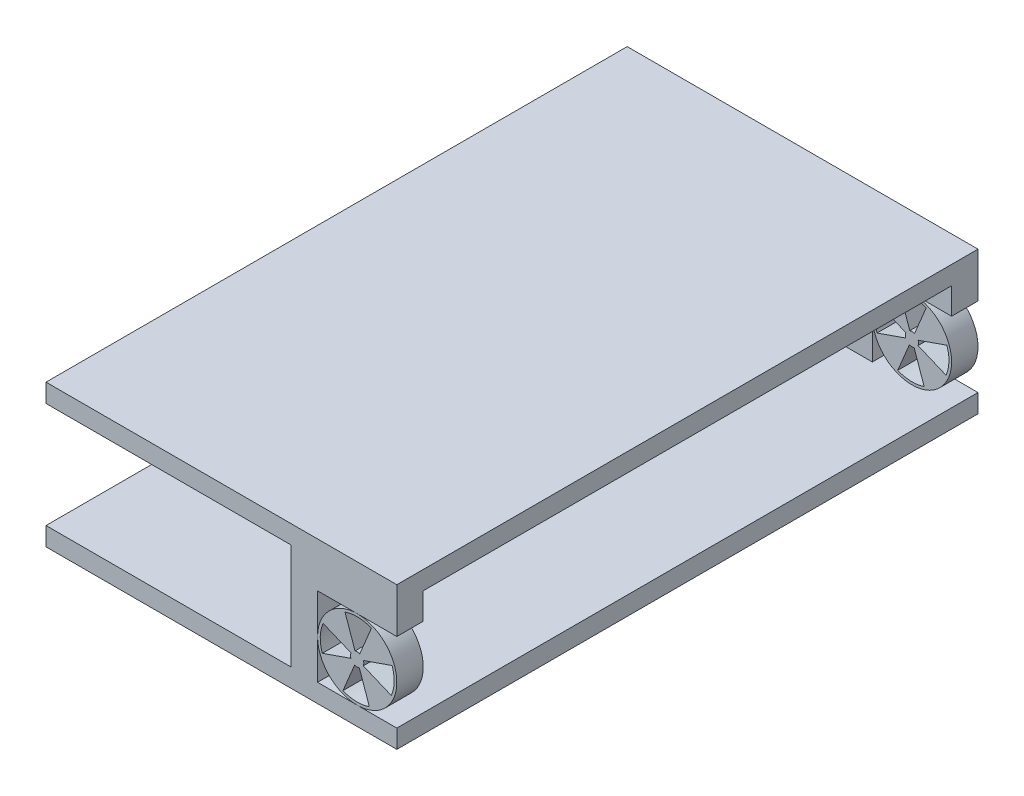
SolidWorks part; units mm, degrees
ref_plane "Front Plane" through (0, 0, 0) normal (0, 0, 1) x (1, 0, 0)
ref_plane "Top Plane" through (0, 0, 0) normal (0, 1, 0) x (1, 0, 0)
ref_plane "Right Plane" through (0, 0, 0) normal (1, 0, 0) x (0, 0, -1)
sketch "Sketch2" plane through (0, 0, 0) normal (0, 1, 0) x (1, 0, 0)
  line L1 (-173.99, 279.4) -> (173.99, 279.4)
  line L2 (-173.99, 279.4) -> (-173.99, -279.4)
  line L3 (-173.99, -279.4) -> (173.99, -279.4)
  line L4 (173.99, 279.4) -> (173.99, -279.4)
  line L5 (-173.99, 279.4) -> (173.99, -279.4) construction
  line L6 (-173.99, -279.4) -> (173.99, 279.4) construction
  point P0 (0, 0)
  dimension "D1" = 558.8
  dimension "D2" = 347.98
extrude "Boss-Extrude1" add sketch "Sketch2" along normal blind 17.78
sketch "Sketch3" plane through (0, 17.78, 0) normal (0, 1, 0) x (1, 0, 0)
  line L0 (72.39, -279.4) -> (72.39, -254)
  line L1 (-173.99, -279.4) -> (173.99, -279.4) construction
  line L2 (72.39, -254) -> (97.79, -254)
  line L3 (97.79, -254) -> (97.79, -279.4)
  line L4 (97.79, -279.4) -> (72.39, -279.4)
  line L5 (173.99, -279.4) -> (173.99, 279.4) construction
  line L6 (0, 0) -> (152.5778, 0) construction
  line L7 (97.79, 254) -> (97.79, 279.4)
  line L8 (97.79, 279.4) -> (72.39, 279.4)
  line L9 (72.39, 279.4) -> (72.39, 254)
  line L10 (72.39, 254) -> (97.79, 254)
  dimension "D1" = 101.6
  dimension "D2" = 76.2
  dimension "D3" = 25.4
extrude "Boss-Extrude2" add sketch "Sketch3" along normal blind 101.6
sketch "Sketch4" plane through (97.79, 0, 0) normal (1, 0, 0) x (0, 0, -1)
  line L0 (-279.4, 119.38) -> (-279.4, 93.98)
  line L1 (-279.4, 119.38) -> (-279.4, 17.78) construction
  line L2 (-279.4, 93.98) -> (-254, 93.98)
  line L3 (-254, 119.38) -> (-254, 17.78) construction
  line L4 (-254, 93.98) -> (-254, 119.38)
  line L5 (-254, 119.38) -> (-279.4, 119.38)
  line L6 (254, 119.38) -> (254, 93.98)
  line L7 (254, 119.38) -> (254, 17.78) construction
  line L8 (254, 93.98) -> (279.4, 93.98)
  line L9 (279.4, 119.38) -> (279.4, 17.78) construction
  line L10 (279.4, 93.98) -> (279.4, 119.38)
  line L11 (279.4, 119.38) -> (254, 119.38)
  dimension "D1" = 25.4
  dimension "D2" = 25.4
extrude "Boss-Extrude3" add sketch "Sketch4" along normal up to vertex (76.2 mm away) up to point (173.99, 17.78, 279.4)
sketch "Sketch5" plane through (0, 0, 0) normal (0, 0, 1) x (1, 0, 0)
  line L0 (135.89, 93.98) -> (135.89, 17.78) construction
  line L1 (173.99, 93.98) -> (97.79, 93.98) construction
  line L2 (97.79, 17.78) -> (173.99, 17.78) construction
  line L3 (97.79, 55.88) -> (178.4367, 55.88) construction
  line L4 (97.79, 93.98) -> (97.79, 17.78) construction
  circle A0 centre (135.89, 55.88) radius 38.1
  dimension "D1" = 76.2
extrude "Boss-Extrude4" add sketch "Sketch5" against normal blind 25.4 from surface separate body starting at face at (68.834, 49.784, 279.4)
extrude "Boss-Extrude5" add sketch "Sketch5<2>" along normal blind 25.4 from surface separate body starting at face at (68.834, 49.784, -279.4)
sketch "Sketch5<2>" plane through (0, 0, 0) normal (0, 0, 1) x (1, 0, 0) same geometry as "Sketch5"
sketch "Sketch6" plane through (0, 0, 279.4) normal (0, 0, 1) x (1, 0, 0)
  line L0 (135.89, 93.98) -> (135.89, 17.78) construction
  line L1 (173.99, 93.98) -> (97.79, 93.98) construction
  line L2 (97.79, 17.78) -> (173.99, 17.78) construction
  line L3 (97.79, 55.88) -> (173.99, 55.88) construction
  line L4 (97.79, 93.98) -> (97.79, 17.78) construction
  line L5 (124.1846, 89.4582) -> (133.7998, 61.8761)
  line L6 (149.5734, 88.7019) -> (138.3335, 61.7411)
  line L7 (169.4682, 67.5854) -> (141.8861, 57.9702)
  line L8 (168.7119, 42.1966) -> (141.7511, 53.4365)
  line L9 (147.5954, 22.3018) -> (137.9802, 49.8839)
  line L10 (122.2066, 23.0581) -> (133.4465, 50.0189)
  line L11 (102.3118, 44.1746) -> (129.8939, 53.7898)
  line L12 (103.0681, 69.5634) -> (130.0289, 58.3235)
  circle A0 centre (135.89, 55.88) radius 38.1 construction
  arc A1 (124.1846, 89.4582) -> (149.5734, 88.7019) centre (135.89, 55.88) cw
  arc A3 (169.4682, 67.5854) -> (168.7119, 42.1966) centre (135.89, 55.88) cw
  arc A5 (147.5954, 22.3018) -> (122.2066, 23.0581) centre (135.89, 55.88) cw
  arc A7 (102.3118, 44.1746) -> (103.0681, 69.5634) centre (135.89, 55.88) cw
  arc A8 (138.3335, 61.7411) -> (133.7998, 61.8761) centre (135.89, 55.88) ccw
  arc A9 (130.0289, 58.3235) -> (129.8939, 53.7898) centre (135.89, 55.88) ccw
  arc A10 (133.4465, 50.0189) -> (137.9802, 49.8839) centre (135.89, 55.88) ccw
  arc A11 (141.7511, 53.4365) -> (141.8861, 57.9702) centre (135.89, 55.88) ccw
  point P37 (135.89, 55.88)
  dimension "D2" = 4
extrude "Cut-Extrude2" cut sketch "Sketch6" against normal blind 1270
extrude "Boss-Extrude6" add sketch "Sketch2<2>" along normal blind 17.78 from surface starting at face at (123.19, 119.38, 266.7)
sketch "Sketch2<2>" plane through (0, 0, 0) normal (0, 1, 0) x (1, 0, 0) same geometry as "Sketch2"
sketch "Sketch7" plane through (0, 0, 0) normal (0, 1, 0) x (1, 0, 0)
  line L0 (-173.99, 279.4) -> (-163.322, 279.4)
  line L1 (173.99, 279.4) -> (-173.99, 279.4) construction
  line L2 (-163.322, 279.4) -> (-163.322, -279.4)
  line L3 (-173.99, -279.4) -> (173.99, -279.4) construction
  line L4 (-163.322, -279.4) -> (-173.99, -279.4)
  line L5 (-173.99, -279.4) -> (-173.99, 279.4)
  dimension "D1" = 10.668
extrude "Cut-Extrude3" cut sketch "Sketch7" along normal blind 381
